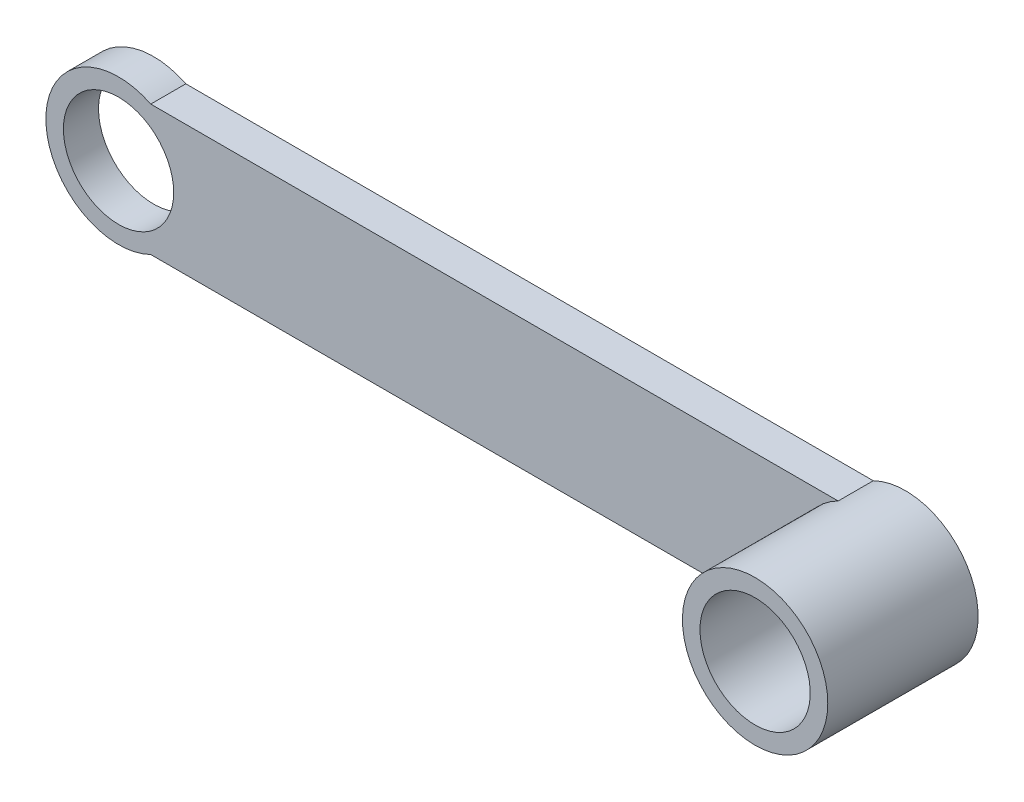
SolidWorks part; units mm, degrees
ref_plane "Front Plane" through (0, 0, 0) normal (0, 0, 1) x (1, 0, 0)
ref_plane "Top Plane" through (0, 0, 0) normal (0, 1, 0) x (1, 0, 0)
ref_plane "Right Plane" through (0, 0, 0) normal (1, 0, 0) x (0, 0, -1)
sketch "Sketch1" plane through (0, 0, 0) normal (0, 0, 1) x (1, 0, 0)
  line L0 (-75, 0) -> (75, 0) construction
  line L2 (-68.5774, 13) -> (68.5774, 13)
  line L3 (-68.5774, 13) -> (-68.5774, -13) construction
  line L4 (-68.5774, -13) -> (68.5774, -13)
  line L5 (68.5774, 13) -> (68.5774, -13) construction
  arc A0 (-68.5774, 13) -> (-68.5774, -13) centre (-75, 0) ccw
  arc A1 (68.5774, -13) -> (68.5774, 13) centre (75, 0) ccw
  point P4 (0, 0)
  point P10 (68.5774, 0)
  dimension "D2" = 29
  dimension "D1" = 150
  dimension "D3" = 26
extrude "Boss-Extrude1" add sketch "Sketch1" along normal blind 7
sketch "Sketch2" plane through (0, 0, 7) normal (0, 0, 1) x (1, 0, 0)
  circle A0 centre (75, 0) radius 14.5
  arc A1 (68.5774, -13) -> (68.5774, 13) centre (75, 0) ccw construction
extrude "Boss-Extrude2" add sketch "Sketch2" along normal blind 23
sketch "Sketch3" plane through (0, 0, 0) normal (0, 0, -1) x (-1, 0, 0)
  circle A0 centre (-75, 0) radius 11
  circle A1 centre (75, 0) radius 11
  dimension "D1" = 22
extrude "Cut-Extrude1" cut sketch "Sketch3" against normal through all
